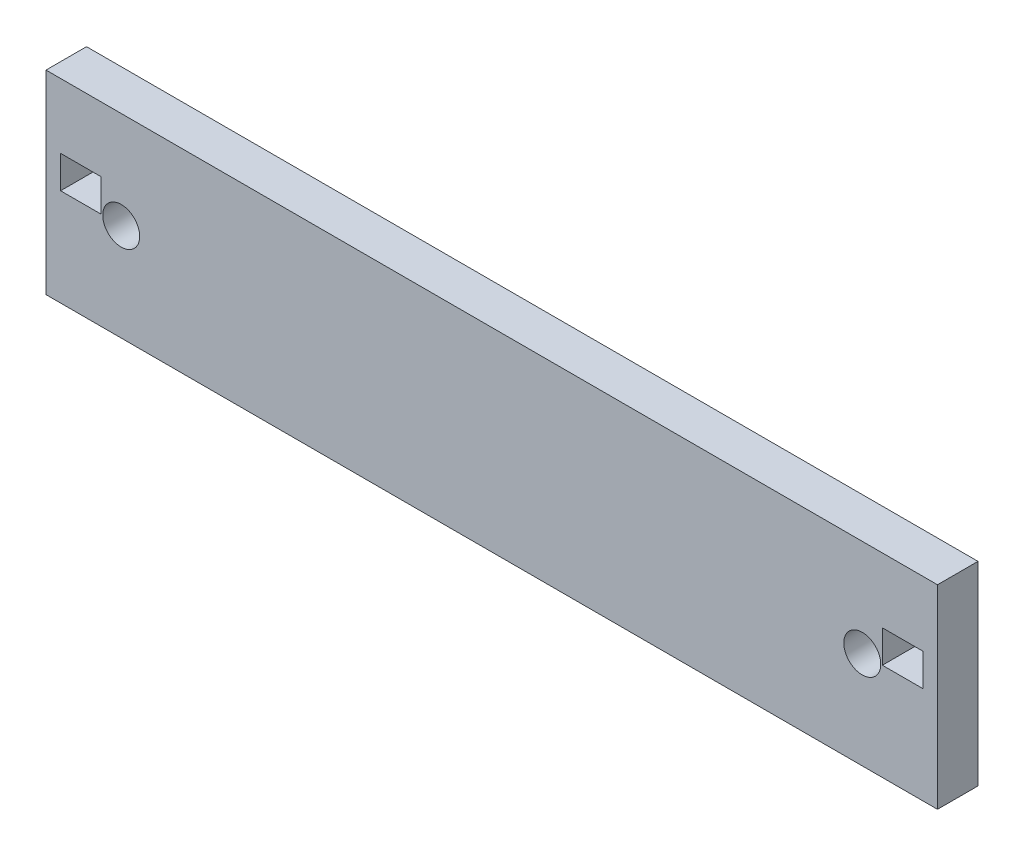
SolidWorks part; units mm, degrees
material "Beech"
ref_plane "Front Plane" through (0, 0, 0) normal (0, 0, 1) x (1, 0, 0)
ref_plane "Top Plane" through (0, 0, 0) normal (0, 1, 0) x (1, 0, 0)
ref_plane "Right Plane" through (0, 0, 0) normal (1, 0, 0) x (0, 0, -1)
sketch "Sketch1" plane through (0, 0, 0) normal (0, 0, 1) x (1, 0, 0)
  line L0 (0, -1000) -> (0, 49000) construction
  line L1 (-19.05, -3.81) -> (15.875, -3.81)
  line L2 (-19.05, -3.81) -> (-19.05, 3.81)
  line L3 (-19.05, 3.81) -> (15.875, 3.81)
  line L4 (15.875, -3.81) -> (15.875, 3.81)
  line L5 (15.3035, 1.27) -> (15.875, 1.27) construction
  line L6 (12.9286, -3.81) -> (12.9286, 0) construction
  line L7 (-18.4785, 0) -> (-16.891, 0)
  line L8 (-18.4785, 0) -> (-18.4785, 1.27)
  line L9 (-18.4785, 1.27) -> (-16.891, 1.27)
  line L10 (-16.891, 0) -> (-16.891, 1.27)
  line L11 (13.716, 0) -> (13.716, 1.27)
  line L12 (15.3035, 1.27) -> (13.716, 1.27)
  line L13 (15.3035, 0) -> (15.3035, 1.27)
  line L14 (15.3035, 0) -> (13.716, 0)
  line L15 (-1000, 0) -> (49000, 0) construction
  line L16 (12.9286, 0) -> (12.9286, 3.81) construction
  line L17 (-18.4785, 1.27) -> (-19.05, 1.27) construction
  circle A0 centre (-16.1036, 0) radius 0.7239
  circle A1 centre (12.9286, 0) radius 0.7239
  point P0 (0, 0)
  dimension "D6" = 1.4478
  dimension "D7" = 0.7874
  dimension "D1" = 0.5715
  dimension "D2" = 7.62
  dimension "D3" = 1.5875
  dimension "D4" = 16.891
  dimension "D5" = 1.27
  dimension "D8" = 13.716
  dimension "D9" = 0.7874
extrude "Boss-Extrude1" add sketch "Sketch1" along normal blind 1.5875
